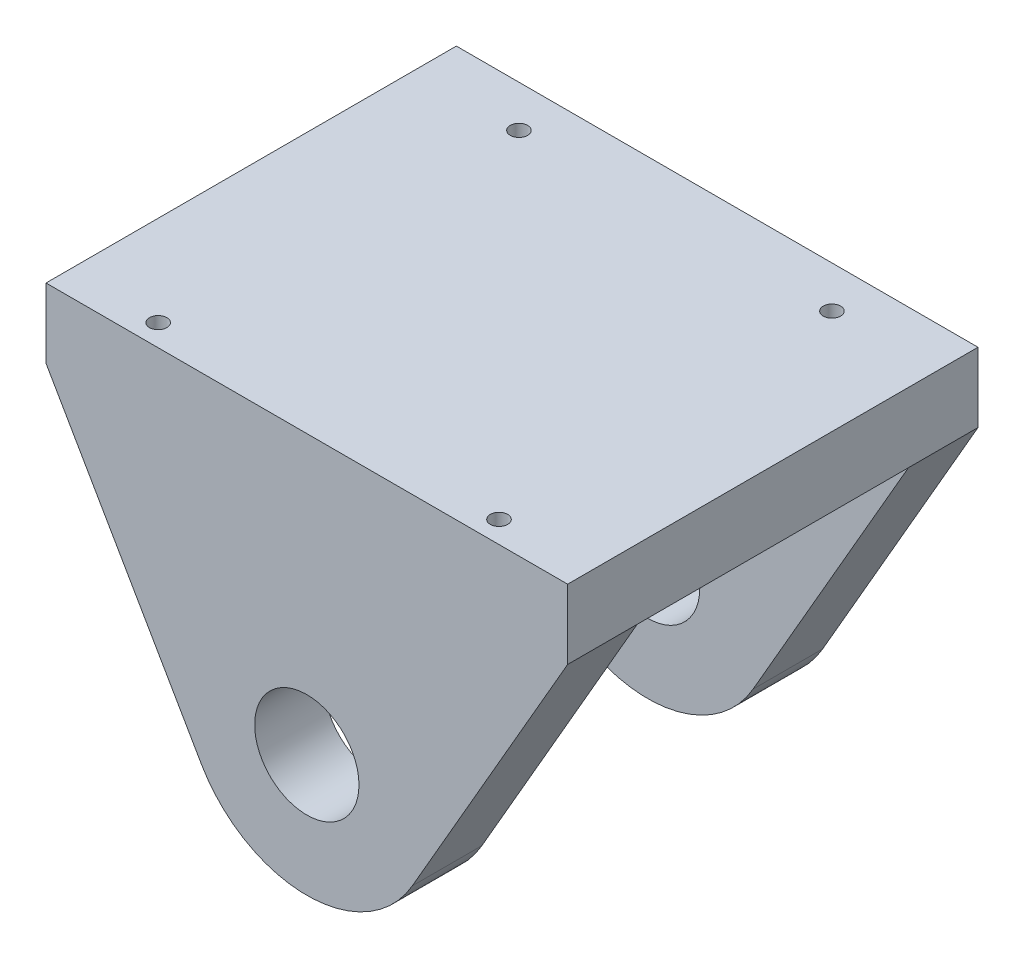
SolidWorks part; units mm, degrees
material "6061 Alloy"
ref_plane "Front Plane" through (0, 0, 0) normal (0, 0, 1) x (1, 0, 0)
ref_plane "Top Plane" through (0, 0, 0) normal (0, 1, 0) x (1, 0, 0)
ref_plane "Right Plane" through (0, 0, 0) normal (1, 0, 0) x (0, 0, -1)
sketch "Sketch1" plane through (0, 0, 0) normal (0, 0, 1) x (1, 0, 0)
  line L0 (-3, 6.8739) -> (3, 6.8739)
  line L1 (-37.5, 30) -> (37.5, 30)
  line L2 (-15.1601, -8.7419) -> (-37.5, 30)
  line L3 (15.1601, -8.7419) -> (37.5, 30)
  line L4 (-37.5, 30) -> (-37.5, 40)
  line L5 (-37.5, 40) -> (37.5, 40)
  line L6 (37.5, 40) -> (37.5, 30)
  circle A0 centre (0, 0) radius 17.5
  circle A1 centre (0, 0) radius 7.5
  dimension "D1" = 35
  dimension "D2" = 15
  dimension "D3" = 6
  dimension "D4" = 30
  dimension "D5" = 75
  dimension "D7" = 10
extrude "Boss-Extrude1" add sketch "Sketch1" against normal blind 10 contours A0 L3 L1 L2 | A0 A1 region at (0, 19.7022, 0) region at (-4.3968, 16.4268, 0)
extrude "Boss-Extrude2" add sketch "Sketch1<3>" against normal blind 59 contours L6 L5 L4 L1 region at (0, 35, 0)
sketch "Sketch1<3>" plane through (0, 0, 0) normal (0, 0, 1) x (1, 0, 0) same geometry as "Sketch1"
ref_plane "Plane2" through (0, 0, -29.5) normal (0, 0, 1) x (1, 0, 0)
mirror "Mirror2" about plane through (0, 0, -29.5) normal (0, 0, 1) of "Boss-Extrude1"
hole_wizard "Tap Drill for M3x0.5 Tap1" positions "Sketch2" profile "Sketch3" hole size "M3x0.5" standard "ANSI Metric"
sketch "Sketch2" plane through (0, 40, 0) normal (0, 1, 0) x (1, 0, 0)
  line L0 (-37.5, 53) -> (37.5, 53) construction
  line L1 (-37.5, 59) -> (-37.5, 0) construction
  line L2 (37.5, 59) -> (37.5, 0) construction
  line L4 (-24.5, 59) -> (-24.5, 0) construction
  line L5 (-37.5, 59) -> (37.5, 59) construction
  line L6 (-37.5, 0) -> (37.5, 0) construction
  line L9 (24.5, 59) -> (24.5, 0) construction
  line L11 (-37.5, 3.13) -> (37.5, 3.13) construction
  line L17 (-22.5, 59) -> (-22.5, 53) construction
  line L20 (22.5, 59) -> (22.5, 53) construction
  point P0 (-22.5, 53)
  point P2 (22.5, 53)
  point P4 (-24.5, 3.13)
  point P6 (24.5, 3.13)
  dimension "D1" = 6
  dimension "D2" = 13
  dimension "D3" = 13
  dimension "D4" = 3.13
  dimension "D5" = 15
  dimension "D6" = 15
sketch "Sketch3" plane through (-22.5, 40, -53) normal (1, 0, 0) x (0, 0, 1)
  line L0 (0, 0) -> (0, 8.7511)
  line L1 (0, 8.7511) -> (1.25, 8)
  line L2 (1.25, 8) -> (1.25, 0)
  line L5 (1.25, 0) -> (0, 0)
  line L10 (0, 8.7511) -> (-1.25, 8) construction
  line L11 (0, -6.35) -> (0, 107.95) construction
  dimension "Hole Dia." = 2.5
  dimension "Hole Depth" = 8
  dimension "Drill Angle" = 118
